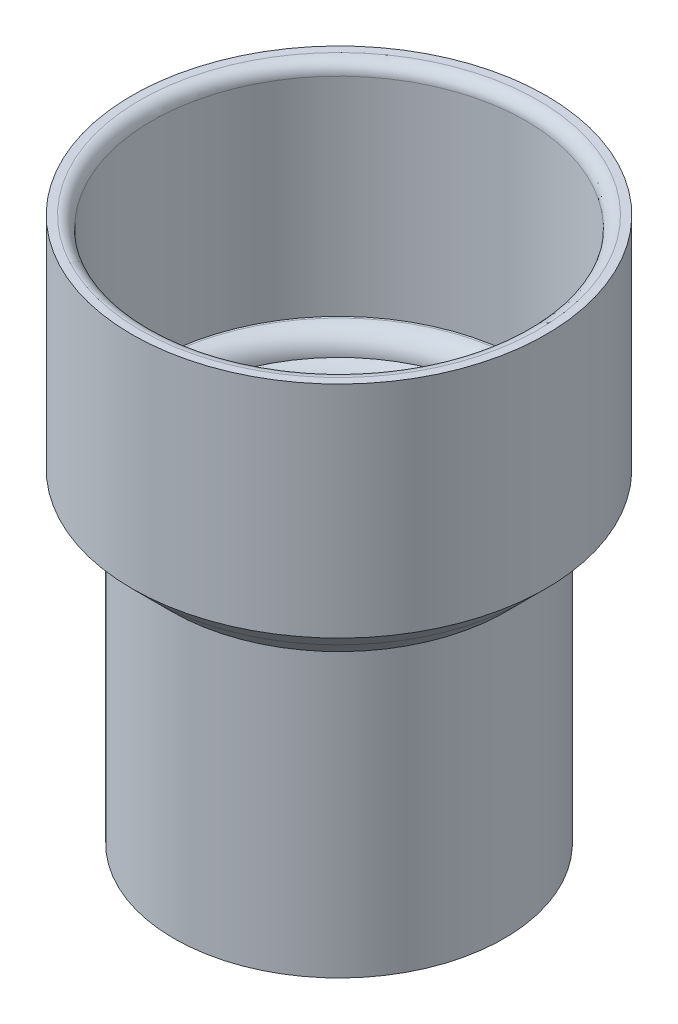
SolidWorks part; units mm, degrees
ref_plane "Front Plane" through (0, 0, 0) normal (0, 0, 1) x (1, 0, 0)
ref_plane "Top Plane" through (0, 0, 0) normal (0, 1, 0) x (1, 0, 0)
ref_plane "Right Plane" through (0, 0, 0) normal (1, 0, 0) x (0, 0, -1)
sketch "Sketch1" plane through (0, 0, 0) normal (0, 1, 0) x (1, 0, 0)
  circle A0 centre (0, 0) radius 37.5
  circle A1 centre (0, 0) radius 41.25
  dimension "D1" = 75
  dimension "D2" = 82.5
extrude "Boss-Extrude2" add sketch "Sketch1" along normal blind 76
sketch "Sketch2" plane through (0, 76, 0) normal (0, 1, 0) x (1, 0, 0)
  circle A0 centre (0, 0) radius 46.75
  circle A1 centre (0, 0) radius 51.75
  dimension "D1" = 93.5
  dimension "D2" = 103.5
extrude "Boss-Extrude3" add sketch "Sketch2" along normal blind 60 separate body
sketch "Sketch3" plane through (0, 76, 0) normal (0, 1, 0) x (1, 0, 0)
  circle A0 centre (0, 0) radius 41.25
  circle A1 centre (0, 0) radius 46.75
extrude "Boss-Extrude5" add sketch "Sketch3" along normal blind 5 and the other way blind 5
chamfer "Chamfer1" distance 5 angle 45 1 edges at (0, 71, 46.75)
chamfer "Chamfer2" distance 5 angle 45 1 edges at (0, 76, 51.75)
fillet "Fillet1" radius 5 1 edges at (0, 81, 41.25)
fillet "Fillet2" radius 5 1 edges at (0, 76, 37.5)
fillet "Fillet3" radius 3 1 edges at (0, 136, 46.75)
